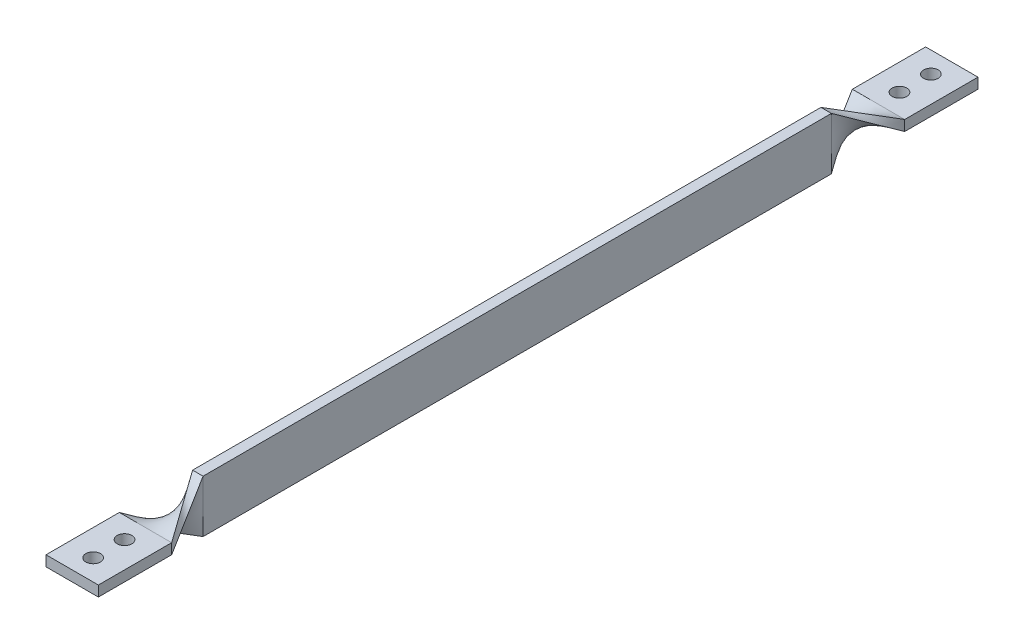
SolidWorks part; units mm, degrees
ref_plane "Płaszczyzna przednia" through (0, 0, 0) normal (0, 0, 1) x (1, 0, 0)
ref_plane "Płaszczyzna górna" through (0, 0, 0) normal (0, 1, 0) x (1, 0, 0)
ref_plane "Płaszczyzna prawa" through (0, 0, 0) normal (1, 0, 0) x (0, 0, -1)
sketch "Szkic1" plane through (0, 0, 0) normal (0, 0, 1) x (1, 0, 0)
  line L1 (0, 0) -> (25, 0)
  line L2 (0, 0) -> (0, 5)
  line L3 (0, 5) -> (25, 5)
  line L4 (25, 0) -> (25, 5)
  dimension "D1" = 25
  dimension "D2" = 5
extrude "Dodanie-wyciągnięcie1" add sketch "Szkic1" along normal mid plane 35
ref_plane "Płaszczyzna1" through (0, 0, 42.5) normal (0, 0, 1) x (1, 0, 0)
sketch "Szkic2" plane through (0, 0, 42.5) normal (0, 0, 1) x (1, 0, 0)
  line L0 (0, 5) -> (0, 0) construction
  line L1 (10, 15) -> (15, 15)
  line L2 (10, 15) -> (10, -10)
  line L3 (10, -10) -> (15, -10)
  line L4 (15, 15) -> (15, -10)
  line L5 (0, 0) -> (25, 0) construction
  dimension "D1" = 5
  dimension "D2" = 25
  dimension "D3" = 10
  dimension "D4" = 10
extrude "Dodanie-wyciągnięcie2" add sketch "Szkic2" along normal blind 300 separate body
loft "Wyciągnięcie po profilach3" add section face at (12.5, 2.5, 17.5) section face at (12.5, 2.5, 42.5) connector at (25, 0, 17.5) connector at (15, 15, 42.5)
ref_plane "Płaszczyzna2" through (0, 0, 367.5) normal (0, 0, 1) x (1, 0, 0)
sketch "Szkic5" plane through (0, 0, 367.5) normal (0, 0, 1) x (1, 0, 0)
  line L1 (0, 5) -> (25, 5)
  line L2 (0, 5) -> (0, 0)
  line L3 (0, 0) -> (25, 0)
  line L4 (25, 5) -> (25, 0)
extrude "Dodanie-wyciągnięcie3" add sketch "Szkic5" along normal blind 35 separate body
loft "Wyciągnięcie po profilach5" add section face at (12.5, 2.5, 367.5) section face at (12.5, 2.5, 342.5) connector at (25, 0, 367.5) connector at (15, 15, 342.5)
sketch "Szkic12" plane through (0, 5, 0) normal (0, 1, 0) x (1, 0, 0)
sketch "Sketch1" plane through (0, 5, 0) normal (0, 1, 0) x (1, 0, 0)
  line L0 (12.5, 17.5) -> (12.5, -402.5) construction
  line L1 (25, 17.5) -> (0, 17.5) construction
  line L2 (25, -402.5) -> (0, -402.5) construction
  line L3 (25, -367.5) -> (0, -367.5) construction
  line L4 (25, -17.5) -> (0, -17.5) construction
  circle A0 centre (12.5, -7.5) radius 3.5
  circle A1 centre (12.5, 7.5) radius 3.5
  circle A2 centre (12.5, -392.5) radius 3.5
  circle A3 centre (12.5, -377.5) radius 3.5
  dimension "D1" = 10
  dimension "D2" = 15
  dimension "D3" = 15
  dimension "D4" = 10
extrude "Cut-Extrude1" cut sketch "Sketch1" against normal blind 10
